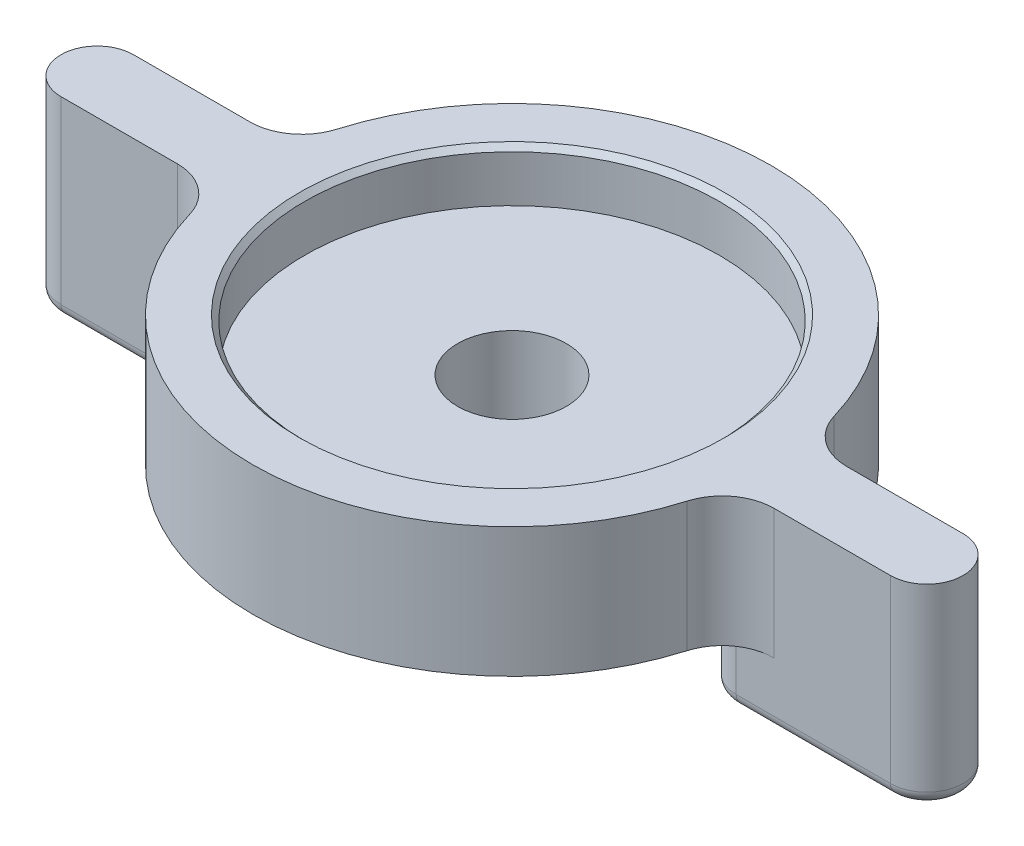
SolidWorks part; units mm, degrees
ref_plane "Plan de face" through (0, 0, 0) normal (0, 0, 1) x (1, 0, 0)
ref_plane "Plan de dessus" through (0, 0, 0) normal (0, 1, 0) x (1, 0, 0)
ref_plane "Plan de droite" through (0, 0, 0) normal (1, 0, 0) x (0, 0, -1)
sketch "Esquisse1" plane through (0, 0, 0) normal (0, 1, 0) x (1, 0, 0)
  circle A0 centre (0, 0) radius 10
  circle A1 centre (0, 0) radius 2.1
  dimension "D1" = 20
  dimension "D2" = 4.2
extrude "Boss.-Extru.1" add sketch "Esquisse1" along normal blind 3
sketch "Esquisse2" plane through (0, 0, 0) normal (0, 1, 0) x (1, 0, 0)
  line L0 (-9.9015, 0) -> (-16, 0) construction
  line L1 (-9.9015, -1.4) -> (-16, -1.4)
  line L2 (-9.9015, 1.4) -> (-16, 1.4)
  line L3 (0, 0) -> (0, 19.6918) construction
  line L4 (9.9015, 0) -> (16, 0) construction
  line L5 (9.9015, -1.4) -> (16, -1.4)
  line L6 (9.9015, 1.4) -> (16, 1.4)
  arc A0 (-9.9015, -1.4) -> (-9.9015, 1.4) centre (-9.9015, 0) ccw
  arc A1 (-16, 1.4) -> (-16, -1.4) centre (-16, 0) ccw
  circle A2 centre (0, 0) radius 10 construction
  arc A3 (9.9015, -1.4) -> (9.9015, 1.4) centre (9.9015, 0) cw
  arc A4 (16, 1.4) -> (16, -1.4) centre (16, 0) cw
  point P3 (-12.9508, 0)
  point P14 (12.9508, 0)
  dimension "D2" = 1.4
  dimension "D1" = 16
extrude "Boss.-Extru.2" add sketch "Esquisse2" along normal blind 5
sketch "Esquisse3" plane through (0, 0, 0) normal (0, -1, 0) x (1, 0, 0)
  line L0 (-10.05, 0) -> (-16, 0) construction
  line L1 (-10.05, -1.4) -> (-16, -1.4)
  line L2 (-10.05, 1.4) -> (-16, 1.4)
  line L3 (0, 0) -> (0, -13.6177) construction
  line L4 (10.05, 0) -> (16, 0) construction
  line L5 (10.05, -1.4) -> (16, -1.4)
  line L6 (10.05, 1.4) -> (16, 1.4)
  arc A0 (-10.05, -1.4) -> (-10.05, 1.4) centre (-10.05, 0) ccw
  arc A1 (-16, 1.4) -> (-16, -1.4) centre (-16, 0) ccw
  arc A2 (-16, 1.4) -> (-16, -1.4) centre (-16, 0) ccw construction
  arc A3 (10.05, -1.4) -> (10.05, 1.4) centre (10.05, 0) cw
  arc A4 (16, 1.4) -> (16, -1.4) centre (16, 0) cw
  point P3 (-13.025, 0)
  point P15 (13.025, 0)
  dimension "D1" = 5.95
extrude "Boss.-Extru.3" add sketch "Esquisse3" along normal blind 2.45
sketch "Esquisse4" plane through (0, 3, 0) normal (0, 1, 0) x (1, 0, 0)
  circle A0 centre (0, 0) radius 10
  circle A1 centre (0, 0) radius 8
  circle A2 centre (0, 0) radius 10 construction
  dimension "D1" = 2
extrude "Boss.-Extru.4" add sketch "Esquisse4" along normal blind 2
fillet "Congé5" radius 2 1 edges at (9.9015, 2.5, -1.4)
fillet "Congé6" radius 2 1 edges at (9.9015, 2.5, 1.4)
fillet "Congé7" radius 2 1 edges at (-9.9015, 2.5, -1.4)
fillet "Congé8" radius 2 1 edges at (-9.9015, 2.5, 1.4)
fillet "Congé10" radius 0.5 8 edges at (17.4, -2.45, 0) (13.025, -2.45, -1.4) (8.65, -2.45, 0) (-8.65, -2.45, 0) (-13.025, -2.45, -1.4) (-17.4, -2.45, 0) (13.025, -2.45, 1.4) (-13.025, -2.45, 1.4)
chamfer "Chanfrein1" distance 0.2 angle 45 1 edges at (0, 5, 8)
